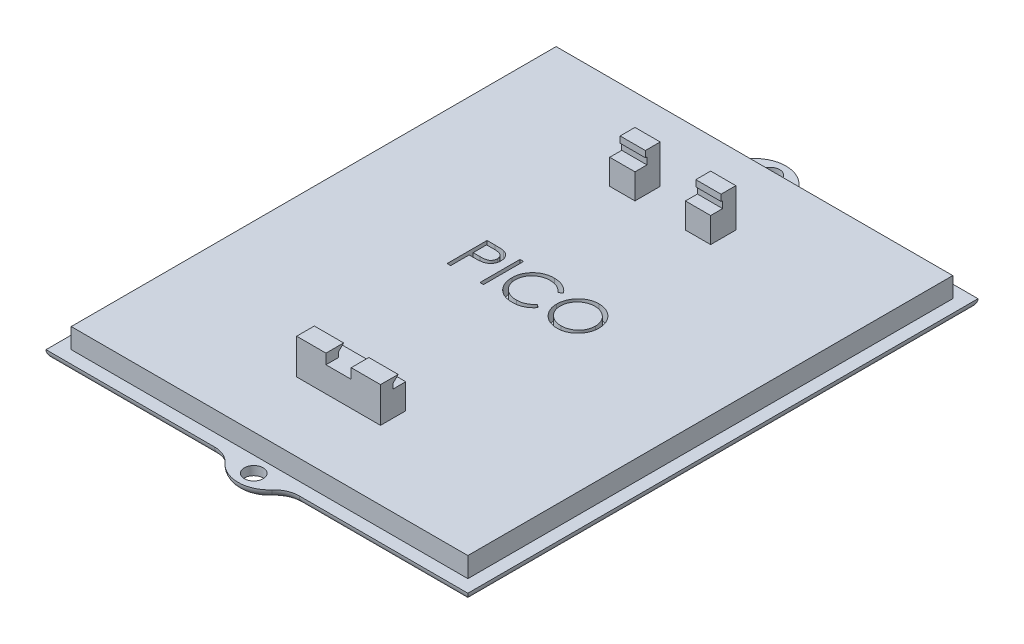
SolidWorks part; units mm, degrees
ref_plane "Front Plane" through (0, 0, 0) normal (0, 0, 1) x (1, 0, 0)
ref_plane "Top Plane" through (0, 0, 0) normal (0, 1, 0) x (1, 0, 0)
ref_plane "Right Plane" through (0, 0, 0) normal (1, 0, 0) x (0, 0, -1)
sketch "Sketch1" plane through (0, 0, 0) normal (0, 1, 0) x (1, 0, 0)
  line L0 (-31.45, 38.45) -> (31.45, 38.45)
  line L5 (-31.45, 38.45) -> (-31.45, -38.45)
  line L6 (-31.45, -38.45) -> (31.45, -38.45)
  line L7 (31.45, 38.45) -> (31.45, -38.45)
  point P11 (-31.45, 0)
  point P12 (0, -38.45)
  dimension "D3" = 76.9
  dimension "D4" = 62.9
extrude "Boss-Extrude1" add sketch "Sketch1" along normal blind 4.575
sketch "Sketch11" plane through (0, 0, 0) normal (0, -1, 0) x (-1, 0, 0)
  line L0 (-31.45, 38.45) -> (31.45, 38.45) construction
  line L1 (-33.45, -40.45) -> (33.45, -40.45)
  line L2 (-33.45, -40.45) -> (-33.45, 40.45)
  line L3 (-33.45, 40.45) -> (33.45, 40.45)
  line L4 (33.45, -40.45) -> (33.45, 40.45)
  line L5 (-31.45, -38.45) -> (-31.45, 38.45) construction
  line L6 (31.45, -38.45) -> (-31.45, -38.45) construction
  line L13 (31.45, 38.45) -> (31.45, -38.45) construction
  dimension "D1" = 2
  dimension "D2" = 2
  dimension "D3" = 2
  dimension "D4" = 2
extrude "Boss-Extrude5" add sketch "Sketch11" against normal blind 1.4
sketch "Sketch4" plane through (0, 0, 0) normal (0, 1, 0) x (1, 0, 0)
  line L2 (-31.45, -38.45) -> (31.45, -38.45) construction
  line L3 (33.45, -40.45) -> (-33.45, -40.45) construction
  line L5 (-6.7082, -40.45) -> (6.7082, -40.45)
  arc A3 (-6.7082, -40.45) -> (-3.7268, -41.7833) centre (-6.7082, -44.45) cw
  arc A4 (-3.7268, -41.7833) -> (3.7268, -41.7833) centre (0, -38.45) ccw
  arc A5 (3.7268, -41.7833) -> (6.7082, -40.45) centre (6.7082, -44.45) cw
  dimension "D1" = 5
  dimension "D4" = 4
extrude "Boss-Extrude3" add sketch "Sketch4" along normal blind 1.4
sketch "Sketch12" plane through (0, 1.4, 0) normal (0, 1, 0) x (1, 0, 0)
  line L0 (0, -38.45) -> (0, -43.45) construction
  line L1 (-31.45, -38.45) -> (31.45, -38.45) construction
  arc A0 (-3.7268, -41.7833) -> (3.7268, -41.7833) centre (0, -38.45) ccw construction
  circle A1 centre (0, -40.95) radius 1.5
  dimension "D1" = 3
extrude "Cut-Extrude3" cut sketch "Sketch12" against normal up to next
mirror "Mirror1" about plane through (0, 0, 0) normal (0, 0, 1) of "Cut-Extrude3", "Boss-Extrude3"
fillet "Fillet1" radius 1.4 12 edges at (20.0791, 0, -40.45) (5.0752, 0, -40.7985) (0, 0, -43.45) (-5.0752, 0, -40.7985) (-20.0791, 0, -40.45) (-33.45, 0, 0) (-20.0791, 0, 40.45) (-5.0752, 0, 40.7985) (0, 0, 43.45) (5.0752, 0, 40.7985) (20.0791, 0, 40.45) (33.45, 0, 0)
sketch "Sketch2" plane through (0, 4.575, 0) normal (0, 1, 0) x (1, 0, 0)
  line L1 (-5.7, 23.5) -> (5.7, 23.5) construction
  line L2 (5.7, 23.5) -> (5.7, -23.5) construction
  line L3 (5.7, -23.5) -> (-5.7, -23.5) construction
  line L4 (-5.7, -23.5) -> (-5.7, 23.5) construction
  circle A8 centre (-5.7, 23.5) radius 1
  circle A9 centre (5.7, 23.5) radius 1
  circle A10 centre (-5.7, -23.5) radius 1
  circle A11 centre (5.7, -23.5) radius 1
  circle A12 centre (-5.7, -23.5) radius 2.5
  circle A13 centre (5.7, -23.5) radius 2.5
  circle A14 centre (5.7, 23.5) radius 2.5
  circle A15 centre (-5.7, 23.5) radius 2.5
  point P8 (5.7, 0)
  point P9 (0, 23.5)
  dimension "D1" = 2
  dimension "D4" = 1.5
  dimension "D2" = 47
  dimension "D3" = 11.4
sketch "Sketch15" plane through (0, 4.575, 0) normal (0, 1, 0) x (1, 0, 0)
  line L0 (-4, 23.5) -> (4, 23.5) construction
  line L1 (-6.65, -27.5) -> (6.65, -27.5)
  line L2 (-6.65, -27.5) -> (-6.65, -23.5)
  line L3 (-6.65, -23.5) -> (6.65, -23.5)
  line L4 (6.65, -27.5) -> (6.65, -23.5)
  line L5 (-8, 27.5) -> (-4, 27.5)
  line L6 (-8, 27.5) -> (-8, 23.5)
  line L7 (-8, 23.5) -> (-4, 23.5)
  line L8 (-4, 27.5) -> (-4, 23.5)
  line L9 (4, 27.5) -> (8, 27.5)
  line L10 (4, 27.5) -> (4, 23.5)
  line L11 (4, 23.5) -> (8, 23.5)
  line L12 (8, 27.5) -> (8, 23.5)
  line L13 (0, -23.5) -> (0, 23.5) construction
  point P14 (0, 0)
  dimension "D1" = 4
  dimension "D2" = 55
  dimension "D3" = 8
  dimension "D4" = 13.3
  dimension "D5" = 16
extrude "Boss-Extrude7" add sketch "Sketch15" along normal blind 4
sketch "Sketch16" plane through (0, 8.575, 0) normal (0, 1, 0) x (1, 0, 0)
  line L0 (-6.65, -27.5) -> (6.65, -27.5) construction
  line L1 (-6.65, -25.5) -> (-2, -25.5)
  line L2 (-6.65, -25.5) -> (-6.65, -27.5)
  line L3 (-6.65, -27.5) -> (-2, -27.5)
  line L4 (-2, -25.5) -> (-2, -27.5)
  line L11 (-6.65, -23.5) -> (-6.65, -27.5) construction
  dimension "D1" = 2
  dimension "D2" = 2
extrude "Boss-Extrude8" add sketch "Sketch16" along normal blind 0.8
sketch "Sketch17" plane through (-6.65, 0, 0) normal (-1, 0, 0) x (0, 0, 1)
  line L0 (27.5, 9.375) -> (27.5, 10.175)
  line L1 (27.5, 10.175) -> (24.7, 10.175)
  line L2 (24.7, 10.175) -> (25.5, 9.375)
  line L3 (25.5, 9.375) -> (27.5, 9.375)
  line L4 (25.5, 9.375) -> (25.5, 8.575) construction
  dimension "D1" = 45
extrude "Boss-Extrude9" add sketch "Sketch17" against normal up to surface (4.65 mm away) up to face at (-2, 8.975, 26.5)
mirror "Mirror4" about plane through (0, 0, 0) normal (1, 0, 0) of "Boss-Extrude9", "Boss-Extrude8"
sketch "Sketch18" plane through (0, 8.575, 0) normal (0, 1, 0) x (1, 0, 0)
  line L1 (4, 25.4) -> (8, 25.4)
  line L2 (4, 25.4) -> (4, 27.5)
  line L3 (4, 27.5) -> (8, 27.5)
  line L4 (8, 25.4) -> (8, 27.5)
  line L5 (-8, 27.5) -> (-8, 23.5) construction
  line L6 (-4, 27.5) -> (-8, 27.5)
  line L7 (-4, 27.5) -> (-4, 25.4)
  line L8 (-4, 25.4) -> (-8, 25.4)
  line L9 (-8, 27.5) -> (-8, 25.4)
  line L11 (2, -25.5) -> (6.65, -25.5) construction
  line L12 (4, 27.5) -> (4, 23.5) construction
  dimension "D1" = 50.9
extrude "Boss-Extrude10" add sketch "Sketch18" along normal blind 1.1
sketch "Sketch5" plane through (0, 4.575, 0) normal (0, 1, 0) x (1, 0, 0)
  line L0 (-15, 0) -> (15, 0) construction
  text T0 "PICO\r\n" font "Century Gothic" height in points 24
  point P6 (0, 0)
  dimension "D1" = 30
extrude "Letters" cut sketch "Sketch5" against normal blind 2
sketch "Sketch21" plane through (0, 9.675, 0) normal (0, 1, 0) x (1, 0, 0)
  line L0 (-4, 23.5) -> (-4, 25.4) construction
  line L1 (-8, 27.5) -> (-4, 27.5)
  line L2 (-8, 27.5) -> (-8, 25.15)
  line L3 (-8, 25.15) -> (-4, 25.15)
  line L4 (-4, 27.5) -> (-4, 25.15)
  line L5 (8, 23.5) -> (8, 25.4) construction
  line L6 (4, 27.5) -> (8, 27.5)
  line L7 (4, 27.5) -> (4, 25.15)
  line L8 (4, 25.15) -> (8, 25.15)
  line L9 (8, 27.5) -> (8, 25.15)
  line L10 (4, 25.4) -> (8, 25.4) construction
  line L11 (-8, 25.4) -> (-4, 25.4) construction
  dimension "D1" = 0.25
  dimension "D2" = 0.25
extrude "Boss-Extrude11" add sketch "Sketch21" along normal blind 1
